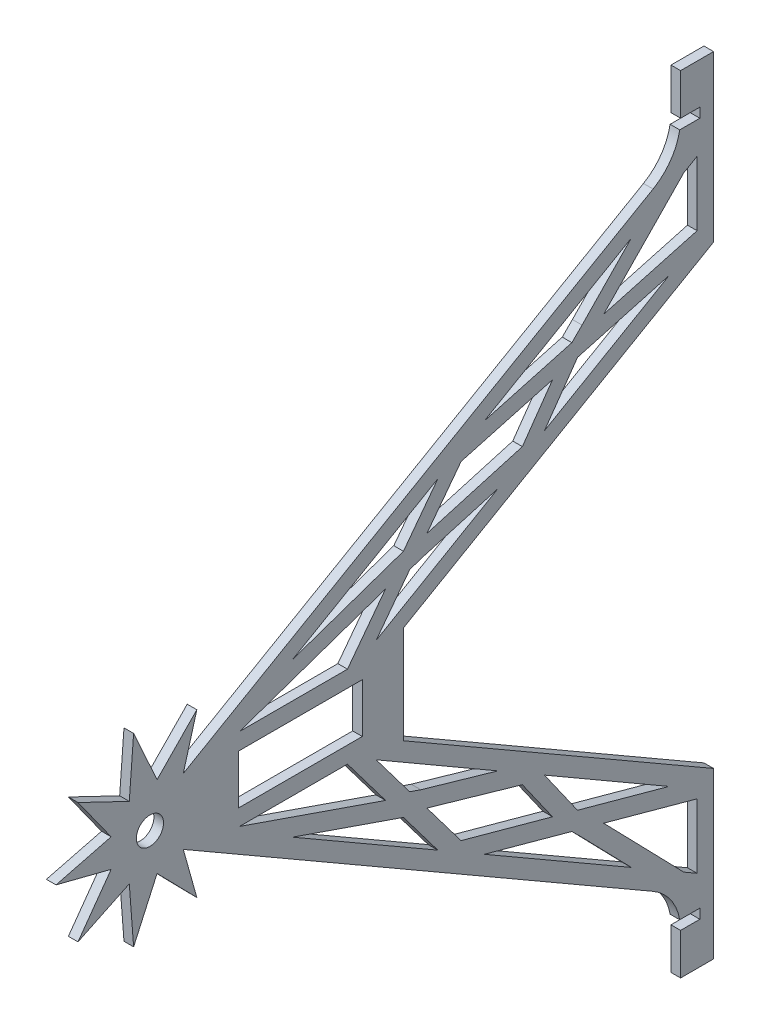
SolidWorks part; units mm, degrees
ref_plane "Front Plane" through (0, 0, 0) normal (1, 0, 0) x (0, 1, 0)
ref_plane "Top Plane" through (0, 0, 0) normal (0, 0, 1) x (0, 1, 0)
ref_plane "Right Plane" through (0, 0, 0) normal (0, 1, 0) x (-1, 0, 0)
sketch "Sketch1" plane through (0, 0, 0) normal (1, 0, 0) x (0, 1, 0)
  line L0 (-4.95, 0) -> (-129.0803, -215) construction
  line L1 (0, -4.95) -> (-121.2724, -215) construction
  line L2 (0, -4.95) -> (121.2724, -215) construction
  line L3 (4.95, 0) -> (129.0803, -215) construction
  line L4 (0, 0) -> (0, -215) construction
  line L5 (-129.0803, -215) -> (129.0803, -215) construction
  line L6 (0, 0) -> (0, -38.94) construction
  line L7 (0, -38.94) -> (0, -77.24) construction
  line L8 (-8.95, -32.14) -> (8.95, -32.14)
  line L9 (-8.95, -32.14) -> (-8.95, -77.24)
  line L10 (-8.95, -77.24) -> (8.95, -77.24)
  line L11 (8.95, -32.14) -> (8.95, -77.24)
  line L12 (-10.8997, -10.3052) -> (-129.0803, -215)
  line L13 (-129.0803, -215) -> (-88.6658, -215)
  line L14 (-88.6658, -215) -> (-17.7903, -92.24)
  line L15 (-17.7903, -92.24) -> (17.7903, -92.24)
  line L16 (17.7903, -92.24) -> (88.6658, -215)
  line L17 (88.6658, -215) -> (129.0803, -215)
  line L18 (129.0803, -215) -> (10.8997, -10.3052)
  circle A0 centre (0, 0) radius 4.95 construction
  circle A1 centre (0, 0) radius 7.5 construction
  arc A2 (-10.8997, -10.3052) -> (10.8997, -10.3052) centre (0, 0) cw
  circle A3 centre (0, 0) radius 4.95
  dimension "D2" = 9.9
  dimension "D3" = 15
  dimension "D9" = 15
  dimension "D10" = 35
  dimension "D1" = 215
  dimension "D4" = 60
  dimension "D5" = 38.94
  dimension "D6" = 45.1
  dimension "D7" = 17.9
  dimension "D8" = 6.8
  dimension "D11" = 35
  dimension "D12" = 15
extrude "Boss-Extrude1" add sketch "Sketch1" along normal blind 3.5
sketch "Sketch2" plane through (3.5, 0, 0) normal (1, 0, 0) x (0, 1, 0)
  line L1 (-129.0803, -215) -> (129.0803, -215)
  line L2 (-129.0803, -215) -> (-129.0803, -205)
  line L3 (-129.0803, -205) -> (129.0803, -205)
  line L4 (129.0803, -215) -> (129.0803, -205)
  dimension "D1" = 10
extrude "Cut-Extrude1" cut sketch "Sketch2" against normal through all both and the other way through all
sketch "Sketch3" plane through (3.5, 0, 0) normal (1, 0, 0) x (0, 0, -1)
  line L1 (205, -82.8923) -> (193, -82.8923)
  line L2 (205, -82.8923) -> (205, -142.8923)
  line L3 (205, -142.8923) -> (193, -142.8923)
  line L4 (193, -82.8923) -> (193, -142.8923)
  line L5 (205, 82.8923) -> (193, 82.8923)
  line L6 (205, 82.8923) -> (205, 142.8923)
  line L7 (205, 142.8923) -> (193, 142.8923)
  line L8 (193, 82.8923) -> (193, 142.8923)
  dimension "D1" = 12
  dimension "D2" = 12
  dimension "D3" = 60
  dimension "D4" = 60
extrude "Boss-Extrude2" add sketch "Sketch3" against normal blind 3.5
fillet "Fillet1" radius 20 2 edges at (1.75, 116.3786, -193) (1.75, -116.3786, -193)
sketch "Sketch4" plane through (3.5, 0, 0) normal (1, 0, 0) x (0, 0, -1)
  line L0 (-7.5, 12.9904) -> (-14.0954, 5.1303) construction
  line L1 (-14.0954, -5.1303) -> (-7.5, -12.9904) construction
  line L2 (-7.5, -12.9904) -> (2.6047, -14.7721) construction
  line L3 (2.6047, -14.7721) -> (11.4907, -9.6418) construction
  line L4 (11.4907, -9.6418) -> (15, 0) construction
  line L5 (15, 0) -> (11.4907, 9.6418) construction
  line L6 (11.4907, 9.6418) -> (2.6047, 14.7721) construction
  line L7 (2.6047, 14.7721) -> (-7.5, 12.9904) construction
  line L8 (-14.0954, 5.1303) -> (-14.0954, -5.1303) construction
  line L9 (15, 0) -> (0, 0) construction
  line L10 (0, 0) -> (-14.0954, -5.1303) construction
  line L11 (0, 0) -> (-14.0954, 5.1303) construction
  line L12 (-14.0954, -5.1303) -> (-34.138, 0)
  line L13 (-34.138, 0) -> (-14.0954, 5.1303)
  line L14 (0, 0) -> (-14.0954, 0)
  line L15 (-14.0954, 0) -> (-34.138, 0)
  line L16 (-14.0954, -5.1303) -> (-14.0954, 5.1303)
  circle A0 centre (0, 0) radius 14.0954 construction
  arc A1 (10.3052, 10.8997) -> (10.3052, -10.8997) centre (0, 0) ccw construction
  arc M29 (10.3052, 10.8997) -> (10.3052, -10.8997) centre (0, 0) ccw
extrude "Boss-Extrude3" add sketch "Sketch4" against normal blind 3.5 contours L15 L13 M29 | L15 L12 M29 region at (3.5, -1.6958, 21.1835) region at (3.5, 1.6958, 21.1835)
ref_axis "Axis1" through (-0.1752, 0, 0) along (1, 0, 0)
pattern_circular "CirPattern1" count 9 over 360 about axis through (-0.1752, 0, 0) along (1, 0, 0) of "Boss-Extrude3"
sketch "Sketch5" plane through (3.5, 0, 0) normal (1, 0, 0) x (0, 0, -1)
  line L0 (205, -142.8923) -> (205, -82.8923) construction
  line L1 (200, -124.3923) -> (183, -124.3923)
  line L2 (200, -124.3923) -> (200, -127.8923)
  line L3 (200, -127.8923) -> (183, -127.8923)
  line L4 (183, -124.3923) -> (183, -127.8923)
  line L5 (193, -142.8923) -> (205, -142.8923) construction
  dimension "D1" = 5
  dimension "D2" = 22
  dimension "D3" = 15
  dimension "D4" = 3.5
extrude "Cut-Extrude2" cut sketch "Sketch5" against normal through all both and the other way through all
mirror "Mirror1" about plane through (0, 0, 0) normal (0, 1, 0) of "Cut-Extrude2"
sketch "Sketch6" plane through (3.5, 0, 0) normal (1, 0, 0) x (0, 1, 0)
  line L8 (-14.95, -75.6035) -> (-86.3564, -199)
  line L9 (-16.7578, -73.2093) -> (-15.4134, -72.1942)
  line L12 (-20.0419, -38.14) -> (-104.6051, -184.6077)
  line L18 (-40.452, -87.9788) -> (-41.913, -92.2033)
  line L19 (-16.7578, -73.2093) -> (-33.3206, -85.7154)
  line L20 (-68.2493, -121.6376) -> (-88.914, -196.9829)
  line L21 (-18.8134, -82.2798) -> (-34.9667, -94.4767)
  line L22 (-59.7005, -113.1525) -> (-68.825, -146.421)
  line L23 (-104.6051, -184.6077) -> (-112.9145, -199)
  line L24 (-102.2289, -186.4817) -> (-110.1106, -194.1434)
  line L25 (-88.914, -196.9829) -> (-89.4672, -199)
  line L26 (-102.2289, -186.4817) -> (-80.1463, -165.0151)
  line L27 (-68.3452, -153.4201) -> (-54.2342, -143.4901)
  line L28 (-44.4406, -126.5659) -> (-36.3741, -98.5461)
  line L29 (-27.9579, -51.8508) -> (-40.452, -87.9788)
  line L30 (-99.0996, -175.072) -> (-80.6727, -157.1591)
  line L31 (-68.825, -146.421) -> (-53.2438, -135.4564)
  line L32 (-53.2438, -135.4564) -> (-43.2459, -100.7281)
  line L33 (-19.1463, -44.7292) -> (-33.3206, -85.7154)
  line L34 (-20.0419, -38.14) -> (-14.95, -29.3407)
  line L35 (-36.3741, -98.5461) -> (-34.9667, -94.4767)
  line L36 (-68.3452, -153.4201) -> (-71.3184, -155.5124)
  line L37 (-80.6727, -157.1591) -> (-76.9784, -153.4648)
  line L38 (-71.3184, -155.5124) -> (-80.4428, -188.7809)
  line L39 (-41.913, -92.2033) -> (-58.4758, -104.7094)
  line L40 (-43.2459, -100.7281) -> (-59.7005, -113.1525)
  line L41 (-14.95, -75.6035) -> (-14.95, -29.3407)
  line L42 (-19.1463, -44.7292) -> (-14.95, -32.5951)
  line L43 (-15.4134, -72.1942) -> (-14.95, -71.8443)
  line L44 (-86.3564, -199) -> (-112.9145, -199)
extrude "Cut-Extrude3" cut sketch "Sketch6" against normal through all both and the other way through all contours L9 L43 L41 L42 L33 L19 | L39 L18 L29 L12 | L35 L28 L8 L21 | L32 L40 L22 L31 | L36 L38 L8 L27 | L30 L37 L20 L12 | L44 L25 L20 L26 L24 L23 region at (3.5, -32.8347, -101.1949) region at (3.5, -21.0735, -63.3849) region at (3.5, -68.6652, -162.5944) region at (3.5, -42.7822, -82.9212) region at (3.5, -94.6864, -187.5516) region at (3.5, -81.4577, -150.1016) region at (3.5, -56.1842, -123.8068)
fillet "Fillet2" [suppressed] radius 2
mirror "Mirror2" about plane through (0, 0, 0) normal (0, 1, 0) of "Cut-Extrude3"
